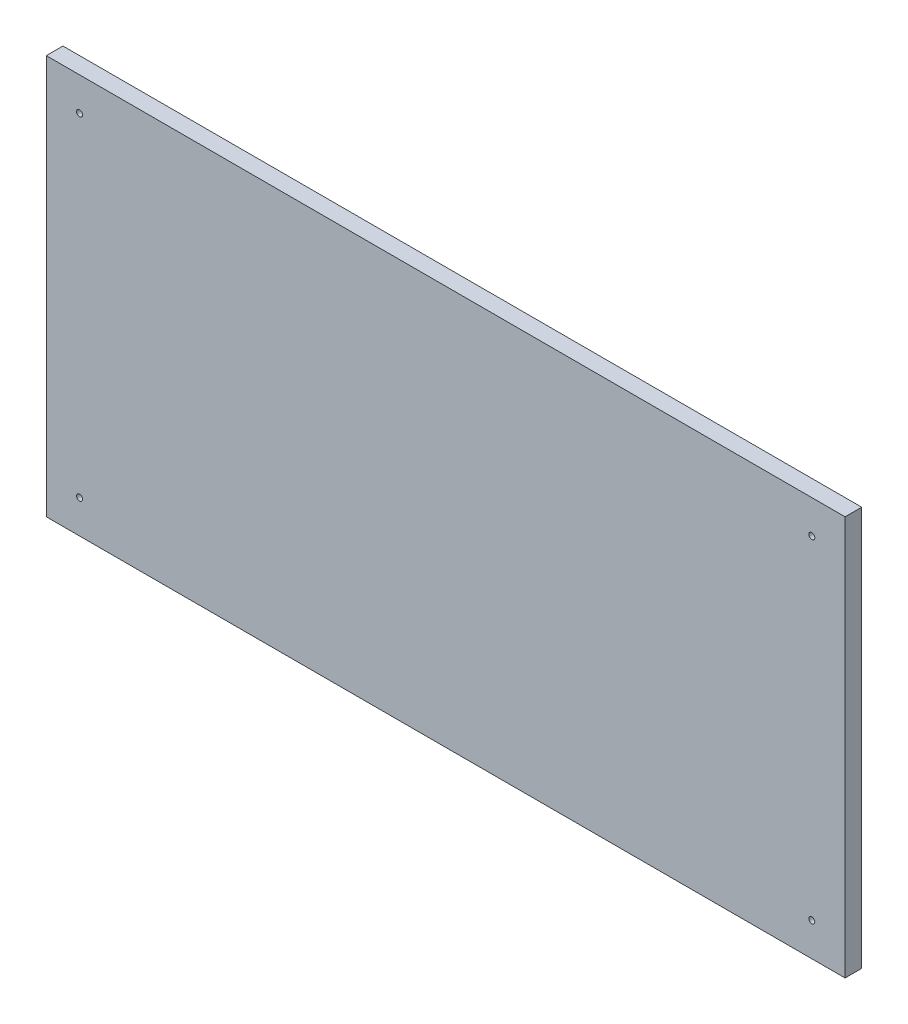
SolidWorks part; units mm, degrees
ref_plane "前视基准面" through (0, 0, 0) normal (0, 0, 1) x (1, 0, 0)
ref_plane "上视基准面" through (0, 0, 0) normal (0, 1, 0) x (1, 0, 0)
ref_plane "右视基准面" through (0, 0, 0) normal (1, 0, 0) x (0, 0, -1)
other "Configuration Table"
sketch "Sketch1" plane through (0, 0, 0) normal (0, 0, 1) x (1, 0, 0)
  line L1 (-600, -300) -> (600, -300)
  line L2 (-600, -300) -> (-600, 300)
  line L3 (-600, 300) -> (600, 300)
  line L4 (600, -300) -> (600, 300)
  line L5 (-600, -300) -> (600, 300) construction
  line L6 (-600, 300) -> (600, -300) construction
  point P0 (0, 0)
extrude "Boss-Extrude1" add sketch "Sketch1" along normal blind 25
sketch "Sketch2" plane through (0, 0, 0) normal (0, 0, 1) x (1, 0, 0)
  circle A0 centre (-550, -250) radius 4.5
extrude "Cut-Extrude1" cut sketch "Sketch2" along normal blind 26
sketch "Sketch3" plane through (0, 0, 0) normal (0, 0, 1) x (1, 0, 0)
  circle A0 centre (550, -250) radius 4.5
extrude "Cut-Extrude2" cut sketch "Sketch3" along normal blind 26
sketch "Sketch4" plane through (0, 0, 0) normal (0, 0, 1) x (1, 0, 0)
  circle A0 centre (-550, 250) radius 4.5
extrude "Cut-Extrude3" cut sketch "Sketch4" along normal blind 26
sketch "Sketch5" plane through (0, 0, 0) normal (0, 0, 1) x (1, 0, 0)
  circle A0 centre (550, 250) radius 4.5
extrude "Cut-Extrude4" cut sketch "Sketch5" along normal blind 26
ref_plane "top_face" through (0, 0, 25) normal (0, 0, 1) x (1, 0, 0)
ref_plane "bottom_face" through (0, 0, 0) normal (0, 0, 1) x (1, 0, 0)
sketch3d "3DSketch1"
  line L0 (-550, -250, 0) -> (-550, -250, 25) construction
ref_axis "hole_axis_fl" through (-550, -250, 0) along (0, 0, 1)
sketch3d "3DSketch2"
  line L0 (550, -250, 0) -> (550, -250, 25) construction
ref_axis "hole_axis_fr" through (550, -250, 0) along (0, 0, 1)
sketch3d "3DSketch3"
  line L0 (-550, 250, 0) -> (-550, 250, 25) construction
ref_axis "hole_axis_bl" through (-550, 250, 0) along (0, 0, 1)
sketch3d "3DSketch4"
  line L0 (550, 250, 0) -> (550, 250, 25) construction
ref_axis "hole_axis_br" through (550, 250, 0) along (0, 0, 1)
